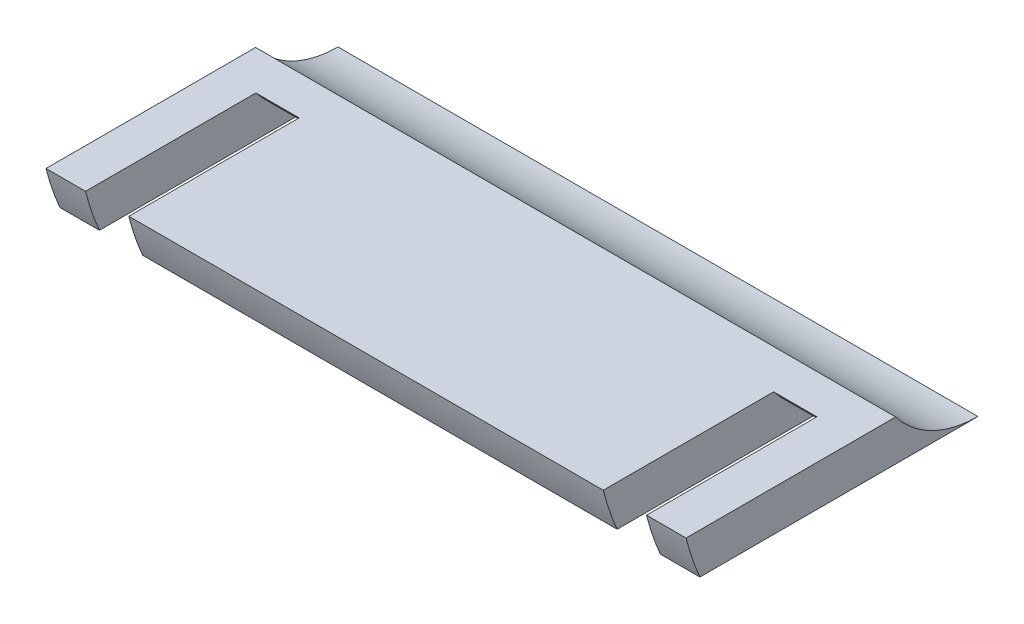
SolidWorks part; units mm, degrees
ref_plane "Front Plane" through (0, 0, 0) normal (0, 0, 1) x (1, 0, 0)
ref_plane "Top Plane" through (0, 0, 0) normal (0, 1, 0) x (1, 0, 0)
ref_plane "Right Plane" through (0, 0, 0) normal (1, 0, 0) x (0, 0, -1)
sketch "Sketch1" plane through (0, 0, 0) normal (0, 1, 0) x (1, 0, 0)
  line L0 (-39.25, 0) -> (39.25, 0)
  line L5 (39.25, 0) -> (39.25, -15.7582)
  line L6 (39.25, -15.7582) -> (34.4, -15.7582)
  line L7 (34.4, -15.7582) -> (34.4, -4.2541)
  line L8 (34.4, -4.2541) -> (29.1, -4.2541)
  line L9 (29.1, -4.2541) -> (29.1, -15.7582)
  line L10 (-39.25, 0) -> (-39.25, -15.7582)
  line L11 (-39.25, -15.7582) -> (-34.4, -15.7582)
  line L12 (-34.4, -15.7582) -> (-34.4, -4.2541)
  line L13 (-34.4, -4.2541) -> (-29.1, -4.2541)
  line L14 (-29.1, -4.2541) -> (-29.1, -15.7582)
  line L15 (-29.1, -15.7582) -> (29.1, -15.7582)
  line L16 (-29.1, -10.0061) -> (29.1, -10.0061) construction
  line L17 (0, 0) -> (0, -10.0061) construction
  line L18 (-29.25, -4.2541) -> (-29.25, -15.7582) construction
  line L19 (-29.25, -15.7582) -> (-29.1, -15.7582) construction
  line L20 (-34.4, -15.7582) -> (-34.25, -15.7582) construction
  line L21 (-34.25, -15.7582) -> (-34.25, -4.2541) construction
  line L22 (29.1, -15.7582) -> (29.25, -15.7582) construction
  line L23 (29.25, -15.7582) -> (29.25, -4.2541) construction
  line L24 (34.25, -4.2541) -> (34.25, -15.7582) construction
  line L25 (34.25, -15.7582) -> (34.4, -15.7582) construction
  point P25 (-21.1115, -4.2541)
  point P26 (-39.438, 0)
  dimension "D1" = 5.3
  dimension "D2" = 5
  dimension "D3" = 0.15
  dimension "D4" = 5
  dimension "D5" = 0.15
  dimension "D6" = 58.5
  dimension "D7" = 5
extrude "Boss-Extrude1" add sketch "Sketch1" along normal blind 5
sketch "Sketch2" plane through (0, 0, 0) normal (1, 0, 0) x (0, 0, -1)
  line L0 (0, 5) -> (-35.0629, 5)
  line L1 (0, 0) -> (-33.3596, 0)
  line L3 (0.7459, 0) -> (0.7459, 5)
  line L4 (0.7459, 5) -> (0, 5)
  line L5 (0.7459, 0) -> (0, 0)
  circle A0 centre (-4.2541, 12.7052) radius 12.7052
  circle A1 centre (-4.2541, 12.7052) radius 31.7578
  circle A4 centre (0.7459, 12.7052) radius 12.7052
  dimension "D1" = 5
  dimension "D2" = 25.4105
  dimension "D3" = 63.5156
  dimension "D4" = 4.2541
  dimension "D5" = 12.7052
extrude "Boss-Extrude2" add sketch "Sketch2" along normal up to surface and the other way up to surface contours L0 A1 L1 A0 | A4 L0 A0 | A4 A0 L1 L5 region at (0, 2.5407, 8.9264) region at (0, 2.3891, 22.6855) region at (0, 0.0744, 1.7541) up to face at (39.25, 2.5, 7.8791) other way up to face at (-39.25, 2.5, 7.8791)
sketch "Sketch4" plane through (-29.1, 0, 0) normal (-1, 0, 0) x (0, 0, 1)
  circle A0 centre (4.2541, 12.7052) radius 31.7578
  circle A1 centre (4.2541, 12.7052) radius 31.7578 construction
  circle A2 centre (4.2541, 12.7052) radius 12.7052 construction
  circle A3 centre (4.2541, 12.7052) radius 12.7052 construction
  circle A4 centre (4.2541, 12.7052) radius 12.5552
  dimension "D1" = 0.15
extrude "Cut-Extrude2" cut sketch "Sketch4" along normal up to surface (5.3 mm away) up to face at (-34.4, 3.565, 6.0405)
extrude "Cut-Extrude3" cut sketch "Sketch4<2>" along normal up to surface (-58.2 mm away) from surface up to face at (29.1, 3.565, 6.0405) starting at face at (34.4, 3.565, 6.0405)
sketch "Sketch4<2>" plane through (-29.1, 0, 0) normal (-1, 0, 0) x (0, 0, 1) same geometry as "Sketch4"
sketch "Sketch3" plane through (0, 0, 0) normal (1, 0, 0) x (0, 0, -1)
  circle A0 centre (0.7459, 12.7052) radius 12.7052
  circle A1 centre (0.7459, 12.7052) radius 12.7052 construction
extrude "Cut-Extrude1" cut sketch "Sketch3" against normal through all both and the other way through all
sketch "Sketch6" plane through (0, 0, 0) normal (1, 0, 0) x (0, 0, -1)
  line L0 (0.7459, 0) -> (-4.2541, 0)
  line L1 (-33.3596, 0) -> (0.7459, 0) construction
  line L2 (0.7459, 12.7052) -> (-4.2541, 12.7052) construction
  line L3 (-4.2541, 0.15) -> (-4.2541, 0)
  circle A0 centre (0.7459, 12.7052) radius 12.7052
  circle A1 centre (-4.2541, 12.7052) radius 12.7052 construction
  arc A2 (-2.133, 0.3305) -> (0.7459, 0) centre (0.7459, 12.7052) ccw construction
  circle A3 centre (-4.2541, 12.7052) radius 12.5552
  dimension "D2" = 0.15
  dimension "D1" = 5
extrude "Boss-Extrude3" add sketch "Sketch6" along normal up to surface and the other way up to surface contours A3 L3 L0 A0 region at (0, 0.1065, 2.3674) up to face at (39.25, 2.1957, 19.4304) other way up to face at (-39.25, 2.1957, 19.4304)
